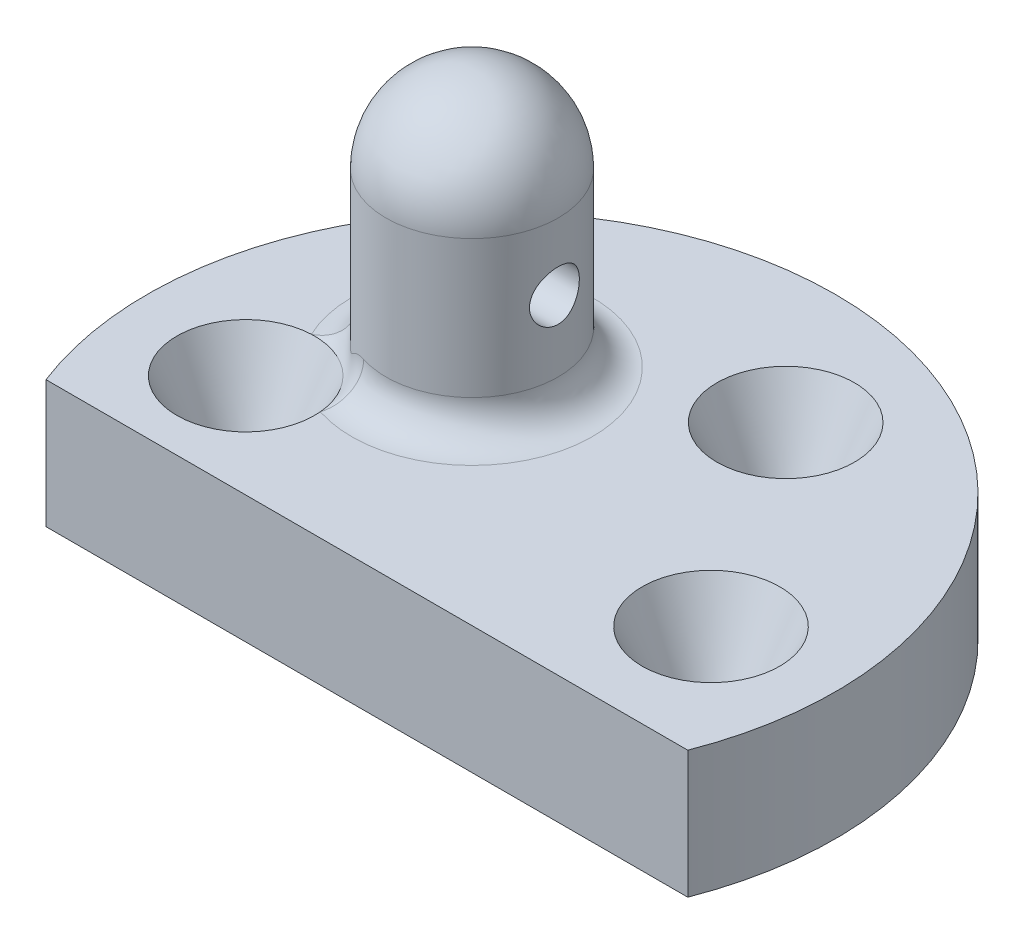
SolidWorks part; units mm, degrees
ref_plane "Plan de face" through (0, 0, 0) normal (0, 0, 1) x (1, 0, 0)
ref_plane "Plan de dessus" through (0, 0, 0) normal (0, 1, 0) x (1, 0, 0)
ref_plane "Plan de droite" through (0, 0, 0) normal (1, 0, 0) x (0, 0, -1)
sketch "Esquisse1" plane through (0, 0, 0) normal (0, 1, 0) x (1, 0, 0)
  line L0 (-18.6474, -7.23) -> (18.6474, -7.23)
  arc A0 (18.6474, -7.23) -> (-18.6474, -7.23) centre (0, 0) ccw
  dimension "D1" = 40
  dimension "D2" = 7.23
extrude "Boss.-Extru.1" add sketch "Esquisse1" along normal blind 7.4
sketch "Esquisse2" plane through (0, 7.4, 0) normal (0, 1, 0) x (1, 0, 0)
  circle A0 centre (-6.9, 5.78) radius 5
  dimension "D1" = 10
  dimension "D2" = 6.9
  dimension "D3" = 5.78
extrude "Boss.-Extru.2" add sketch "Esquisse2" along normal blind 15
sketch "Esquisse3" plane through (0, 7.4, 0) normal (0, 1, 0) x (1, 0, 0)
  line L0 (-18.6474, -7.23) -> (18.6474, -7.23) construction
  circle A0 centre (-13.0421, -1.23) radius 1.95
  arc A1 (18.6474, -7.23) -> (-18.6474, -7.23) centre (0, 0) ccw construction
  circle A2 centre (13.0958, -0.33) radius 1.95
  circle A3 centre (5, 12.1083) radius 1.95
  dimension "D1" = 3.9
  dimension "D4" = 3.9
  dimension "D7" = 3.9
  dimension "D2" = 13.1
  dimension "D3" = 6
  dimension "D5" = 13.1
  dimension "D6" = 6.9
  dimension "D8" = 13.1
  dimension "D9" = 5
extrude "Enlèv. mat.-Extru.1" cut sketch "Esquisse3" against normal through all
sketch "Esquisse4" plane through (0, 7.4, 0) normal (0, 1, 0) x (1, 0, 0)
  circle A0 centre (5, 12.1083) radius 4
  circle A1 centre (-13.0421, -1.23) radius 4
  circle A2 centre (13.0958, -0.33) radius 4
  dimension "D1" = 8
  dimension "D2" = 8
  dimension "D3" = 8
extrude "Enlèv. mat.-Extru.2" cut sketch "Esquisse4" against normal blind 4.4 draft 25
sketch "Esquisse5" plane through (0, 0, 0) normal (1, 0, 0) x (0, 0, -1)
  line L0 (20, 7.4) -> (-7.23, 7.4) construction
  circle A0 centre (5.78, 13.5) radius 1.45
  dimension "D1" = 2.9
  dimension "D2" = 6.1
extrude "Enlèv. mat.-Extru.3" cut sketch "Esquisse5" against normal through all
fillet "Congé1" radius 5 1 edges at (-6.9, 22.4, -0.78)
fillet "Congé2" radius 2 1 edges at (-6.9, 7.4, -0.78)
